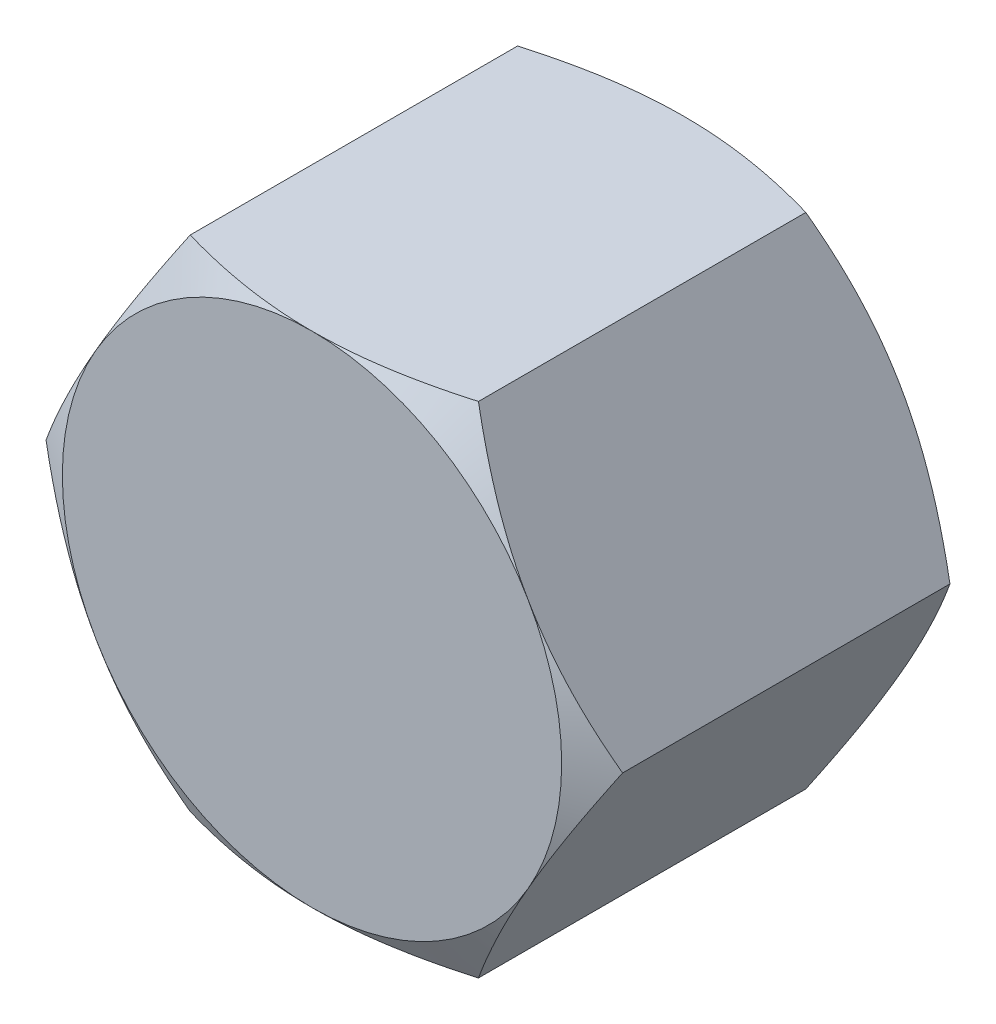
SolidWorks part; units mm, degrees
ref_plane "Front Plane" through (0, 0, 0) normal (0, 0, 1) x (1, 0, 0)
ref_plane "Top Plane" through (0, 0, 0) normal (0, 1, 0) x (1, 0, 0)
ref_plane "Right Plane" through (0, 0, 0) normal (1, 0, 0) x (0, 0, -1)
sketch "Sketch1" plane through (0, 0, 0) normal (0, 0, 1) x (1, 0, 0)
  line L0 (4.65, -8.054) -> (9.3, 0)
  line L1 (9.3, 0) -> (4.65, 8.054)
  line L2 (4.65, 8.054) -> (-4.65, 8.054)
  line L3 (-4.65, 8.054) -> (-9.3, 0)
  line L4 (-9.3, 0) -> (-4.65, -8.054)
  line L5 (-4.65, -8.054) -> (4.65, -8.054)
  line L6 (-9.3, 0) -> (9.3, 0) construction
  circle A0 centre (0, 0) radius 8.054 construction
  dimension "D1" = 18.6
extrude "Boss-Extrude1" add sketch "Sketch1" along normal mid plane 12
sketch "Sketch2" plane through (0, 0, 0) normal (0, 0, 1) x (1, 0, 0)
  line L0 (9.3, 0) -> (4.65, 8.054) construction
  circle A0 centre (0, 0) radius 8.054
extrude "Cut-Extrude5" cut sketch "Sketch2" along normal blind 8 draft 60 from surface flip side to cut starting at face at (0, 0, -6)
sketch "Sketch3" plane through (0, 0, 0) normal (0, 0, 1) x (1, 0, 0)
  line L0 (-9.3, 0) -> (-4.65, -8.054) construction
  circle A0 centre (0, 0) radius 8.054
extrude "Cut-Extrude7" cut sketch "Sketch3" against normal blind 8 draft 60 from surface flip side to cut starting at face at (0, 0, 6)
sketch "Sketch4" plane through (0, 0, 0) normal (0, 0, 1) x (1, 0, 0)
  circle A0 centre (0, 0) radius 5
  dimension "D1" = 10
extrude "Cut-Extrude8" cut sketch "Sketch4" against normal through all both and the other way through all
chamfer "Chamfer1" distance 1 angle 45 2 edges at (5, 0, 6) (5, 0, -6)
thread "Thread1" pitch 1.5 method cut profile "Thread Profile2" start angle 0, offset 0, length 0, pitch 1.5, diameter 10
ref_plane "Plane5" through (5, 0, -6) normal (0, -1, 0) x (1, 0, 0)
sketch "Thread Profile2" plane through (5, 0, -6) normal (0, -1, 0) x (1, 0, 0)
  line L0 (0, 0) -> (0, 1.5) construction
  line L1 (0, 0) -> (0.8119, 0.4687)
  line L2 (0.8119, 0.4687) -> (0.8119, 0.6562)
  line L3 (0.8119, 0.6562) -> (0, 1.125)
  line L4 (0.8119, 0.5625) -> (0, 0.5625) construction
  line L11 (0, 0) -> (0, 1.125)
  point P2 (0, 0)
  dimension "Pitch" = 1.5
  dimension "Profile_Angle" = 60
  dimension "Profile_Land" = 0.1875
  dimension "Profile_Height" = 0.8119
sketch "Sketch5" plane through (0, 0, 6) normal (0, 0, 1) x (1, 0, 0)
  circle A0 centre (0, 0) radius 6
extrude "Boss-Extrude2" add sketch "Sketch5" against normal blind 4
